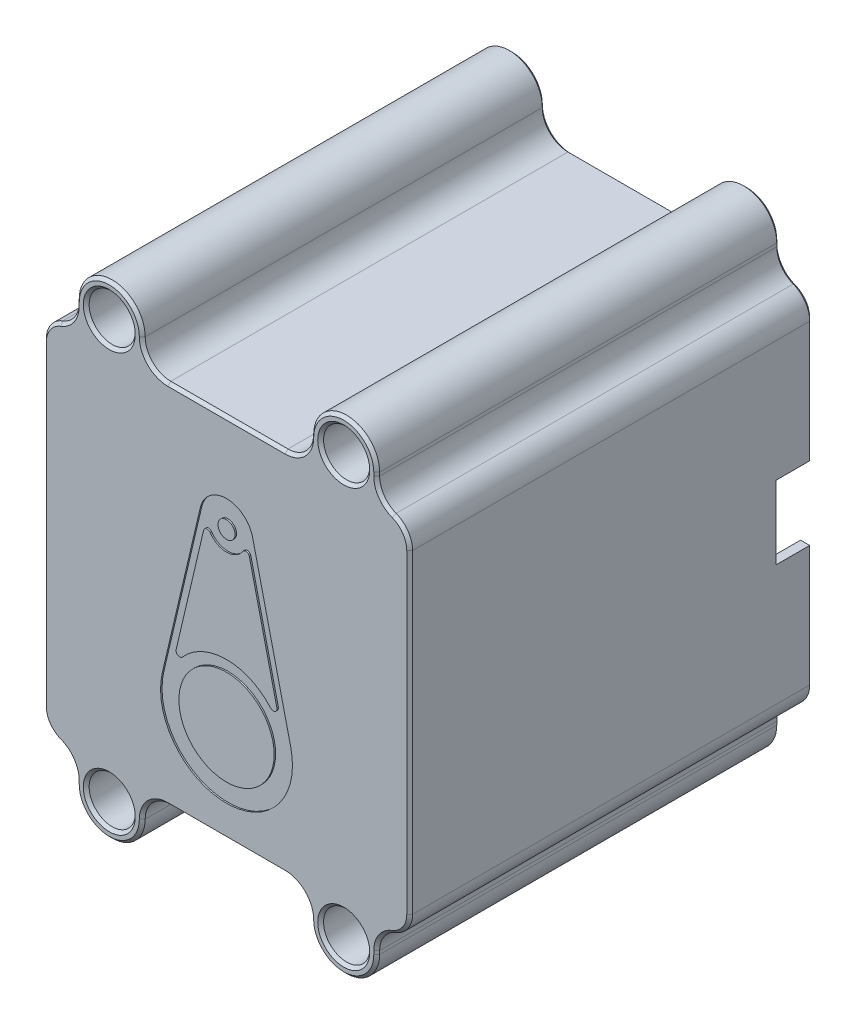
SolidWorks part; units mm, degrees
ref_plane "Front" through (0, 0, 0) normal (0, 0, 1) x (1, 0, 0)
ref_plane "Top" through (0, 0, 0) normal (0, 1, 0) x (1, 0, 0)
ref_plane "Right" through (0, 0, 0) normal (1, 0, 0) x (0, 0, -1)
sketch "Skizze1" plane through (0, 0, 0) normal (0, 0, 1) x (1, 0, 0)
  line L1 (-25, -25) -> (25, -25)
  line L2 (-25, -25) -> (-25, 25)
  line L3 (-25, 25) -> (25, 25)
  line L4 (25, -25) -> (25, 25)
  line L5 (-25, -25) -> (25, 25) construction
  line L6 (-25, 25) -> (25, -25) construction
  line L7 (-23.75, -23.75) -> (23.75, -23.75)
  line L8 (-23.75, -23.75) -> (-23.75, 23.75)
  line L9 (-23.75, 23.75) -> (23.75, 23.75)
  line L10 (23.75, -23.75) -> (23.75, 23.75)
  line L11 (-23.75, -23.75) -> (23.75, 23.75) construction
  line L12 (-23.75, 23.75) -> (23.75, -23.75) construction
  point P0 (0, 0)
  point P6 (0, 0)
  dimension "D1" = 50
  dimension "D2" = 1.25
extrude "Aufsatz-Linear austragen1" add sketch "Skizze1" along normal blind 55
sketch "Skizze2" plane through (0, 0, 55) normal (0, 0, 1) x (1, 0, 0)
  line L1 (-25, 25) -> (25, 25)
  line L2 (-25, 25) -> (-25, -25)
  line L3 (-25, -25) -> (25, -25)
  line L4 (25, 25) -> (25, -25)
extrude "Aufsatz-Linear austragen2" add sketch "Skizze2" against normal blind 1
fillet "Verrundung1" radius 3.5 8 edges at (23.75, -23.75, 27) (-23.75, -23.75, 27) (-23.75, 23.75, 27) (23.75, 23.75, 27) (-25, 25, 27.5) (25, 25, 27.5) (-25, -25, 27.5) (25, -25, 27.5)
sketch "Skizze3" plane through (25, 0, 0) normal (1, 0, 0) x (0, 0, -1)
  line L0 (0, 0) -> (-26.4539, 0) construction
  line L1 (0, -5) -> (0, 5)
  line L2 (0, -21.5) -> (0, 21.5) construction
  line L3 (0, 5) -> (-5, 5)
  line L4 (-5, 5) -> (-5, -5)
  line L5 (0, -5) -> (-5, -5)
  point P9 (-5, 0)
  dimension "D1" = 10
  dimension "D2" = 5
extrude "Schnitt-Linear austragen1" cut sketch "Skizze3" against normal blind 2
chamfer "Fase1" distance 1 angle 45 8 edges at (23.75, 0, 54) (22.7249, 22.7249, 54) (22.7249, -22.7249, 54) (0, 23.75, 54) (0, -23.75, 54) (-22.7249, 22.7249, 54) (-22.7249, -22.7249, 54) (-23.75, 0, 54)
sketch "Skizze4" plane through (0, 0, 0) normal (0, 0, -1) x (-1, 0, 0)
  line L0 (-20.5, 28.5) -> (-20.5, 25)
  line L1 (-21.5, 25) -> (21.5, 25) construction
  line L2 (-11.5, 28.5) -> (-11.5, 25)
  line L3 (-25, 5) -> (-25, 21.5) construction
  line L4 (0, 0) -> (-10.6802, 0) construction
  line L5 (-11.5, 25) -> (-20.5, 25)
  line L6 (-11.5, -28.5) -> (-11.5, -25)
  line L7 (-11.5, -25) -> (-20.5, -25)
  line L8 (-20.5, -28.5) -> (-20.5, -25)
  line L16 (-11.5, 28.5) -> (-11.5, 25)
  line L17 (-11.5, 25) -> (-20.5, 25)
  line L18 (-20.5, 28.5) -> (-20.5, 25)
  line L19 (0, 0) -> (0, 15.2727) construction
  line L20 (20.5, -28.5) -> (20.5, -25)
  line L21 (11.5, -25) -> (20.5, -25)
  line L22 (11.5, -28.5) -> (11.5, -25)
  line L23 (11.5, 28.5) -> (11.5, 25)
  line L24 (11.5, 25) -> (20.5, 25)
  line L25 (20.5, 28.5) -> (20.5, 25)
  circle A0 centre (-16, 28.5) radius 1.8
  circle A1 centre (-16, 28.5) radius 3.15 construction
  arc A2 (-11.5, 28.5) -> (-20.5, 28.5) centre (-16, 28.5) ccw
  arc A3 (-20.5, 28.5) -> (-11.5, 28.5) centre (-16, 28.5) ccw construction
  circle A4 centre (-16, -28.5) radius 1.8
  arc A5 (-11.5, -28.5) -> (-20.5, -28.5) centre (-16, -28.5) cw
  arc A14 (-11.5, 28.5) -> (-20.5, 28.5) centre (-16, 28.5) ccw
  arc A15 (11.5, -28.5) -> (20.5, -28.5) centre (16, -28.5) ccw
  circle A16 centre (16, -28.5) radius 1.8
  circle A17 centre (16, 28.5) radius 1.8
  arc A18 (11.5, 28.5) -> (20.5, 28.5) centre (16, 28.5) cw
  dimension "D1" = 3.6
  dimension "D2" = 6.3
  dimension "D7" = 4.5
  dimension "D3" = 9
  dimension "D4" = 3.5
extrude "Aufsatz-Linear austragen3" add sketch "Skizze4" against normal up to surface (55 mm away)
sketch "Skizze5" plane through (0, 0, 55) normal (0, 0, 1) x (1, 0, 0)
  circle A0 centre (-16, 28.5) radius 3.15
  circle A1 centre (16, 28.5) radius 3.15
  circle A2 centre (16, -28.5) radius 3.15
  circle A3 centre (-16, -28.5) radius 3.15
  dimension "D1" = 6.3
extrude "Schnitt-Linear austragen2" cut sketch "Skizze5" against normal offset from surface (49 mm away) 6 up to face at (2.7083, 0, 0)
chamfer "Fase3" distance 0.67 angle 45 8 edges at (-19.15, 28.5, 6) (-17.8, 28.5, 6) (-17.8, -28.5, 6) (-19.15, -28.5, 6) (12.85, -28.5, 6) (14.2, -28.5, 6) (14.2, 28.5, 6) (12.85, 28.5, 6)
fillet "Verrundung2" radius 3.5 8 edges at (11.5, 25, 27.5) (20.5, 25, 27.5) (20.5, -25, 27.5) (11.5, -25, 27.5) (-11.5, 25, 27.5) (-20.5, 25, 27.5) (-20.5, -25, 27.5) (-11.5, -25, 27.5)
chamfer "Fase2" distance 0.4 angle 45 68 edges at (24.3831, 23.4843, 55) (25, 0, 55) (24.3831, -23.4843, 55) (0, -25, 55) (-24.3831, -23.4843, 55) (-25, 0, 55) (-24.3831, 23.4843, 55) (0, 25, 55) (21.1169, -26.054, 55) (20.5, -28.2692, 0) (20.5, -28.2692, 55) (16, -33, 55) (16, -33, 0) (10.4749, -26.0251, 55) (-10.4749, -26.0251, 55) (-16, -33, 55) (-16, -33, 0) (-20.5, -28.2692, 55) (-20.5, -28.2692, 0) (-21.1169, -26.054, 55) (-21.1169, 26.054, 55) (-20.5, 28.2692, 0) (-20.5, 28.2692, 55) (-16, 33, 55) (-16, 33, 0) (-10.4749, 26.0251, 55) (10.4749, 26.0251, 55) (16, 33, 55) (16, 33, 0) (20.5, 28.2692, 55) (20.5, 28.2692, 0) (21.1169, 26.054, 55) (-12.85, 28.5, 55) (19.15, 28.5, 55) (19.15, -28.5, 55) (-12.85, -28.5, 55) (14.2, -28.5, 0) (-17.8, 28.5, 0) (-17.8, -28.5, 0) (14.2, 28.5, 0) (23.75, -12.625, 0) (22.7249, -22.7249, 0) (0, -23.75, 0) (-22.7249, -22.7249, 0) (-23.75, 0, 0) (-22.7249, 22.7249, 0) (0, 23.75, 0) (22.7249, 22.7249, 0) (23.75, 12.625, 0) (24.375, 5, 0) (25, 13.25, 0) (24.3831, 23.4843, 0) (21.1169, 26.054, 0) (10.4749, 26.0251, 0) (0, 25, 0) (-10.4749, 26.0251, 0) (-21.1169, 26.054, 0) (-24.3831, 23.4843, 0) (-25, 0, 0) (-24.3831, -23.4843, 0) (-21.1169, -26.054, 0) (-10.4749, -26.0251, 0) (0, -25, 0) (10.4749, -26.0251, 0) (21.1169, -26.054, 0) (24.3831, -23.4843, 0) (25, -13.25, 0) (24.375, -5, 0)
sketch "Skizze6" plane through (0, 0, 55) normal (0, 0, 1) x (1, 0, 0)
  line L0 (0, 0) -> (0, 11.6779) construction
  line L1 (0, 0) -> (-30.6037, 0) construction
  line L2 (0, 0) -> (0, -11.6779) construction
  line L3 (-8.7622, -9.6228) -> (-3.5698, 12.5152)
  line L4 (-6.8471, -5.837) -> (-2.5962, 12.2869)
  line L5 (7.7886, -9.8511) -> (2.5962, 12.2869)
  line L6 (8.7622, -9.6228) -> (3.5698, 12.5152)
  line L7 (-7.7886, -9.8511) -> (-6.8471, -5.837)
  arc A0 (-2.5962, 12.2869) -> (2.5962, 12.2869) centre (0, 11.6779) ccw
  arc A1 (7.7886, -9.8511) -> (-7.7886, -9.8511) centre (0, -11.6779) ccw
  circle A2 centre (0, -11.6779) radius 6.5
  circle A3 centre (0, 11.6779) radius 1.1667
  arc A4 (3.5698, 12.5152) -> (-3.5698, 12.5152) centre (0, 11.6779) ccw
  arc A5 (-8.7622, -9.6228) -> (8.7622, -9.6228) centre (0, -11.6779) ccw
  arc A6 (-7.7886, -9.8511) -> (7.7886, -9.8511) centre (0, -11.6779) ccw construction
  arc A7 (-6.8471, -5.837) -> (-8.7622, -9.6228) centre (0, -11.6779) ccw construction
  arc A10 (6.8471, -5.837) -> (0, -2.6779) centre (0, -11.6779) ccw construction
  arc A11 (8.7622, -9.6228) -> (6.8471, -5.837) centre (0, -11.6779) ccw construction
  arc A12 (-3.1709, 9.8368) -> (0, 8.0113) centre (0, 11.6779) ccw construction
  arc A13 (0, 8.0113) -> (3.1709, 9.8368) centre (0, 11.6779) ccw construction
  arc A14 (3.1709, 9.8368) -> (3.5698, 12.5152) centre (0, 11.6779) ccw construction
  arc A15 (-3.5698, 12.5152) -> (-3.1709, 9.8368) centre (0, 11.6779) ccw construction
  arc A16 (2.5962, 12.2869) -> (-2.5962, 12.2869) centre (0, 11.6779) ccw construction
  dimension "D1" = 5.3333
  dimension "D2" = 16
  dimension "D3" = 1.5
  dimension "D4" = 1.5
  dimension "D5" = 1
  dimension "D6" = 1
extrude "Schnitt-Linear austragen4" cut sketch "Skizze6" against normal blind 0.2
fillet "Verrundung3" radius 0.5 4 edges at (7.7886, -9.8511, 54.9) (-7.7886, -9.8511, 54.9) (2.5962, 12.2869, 54.9) (-2.5962, 12.2869, 54.9)
